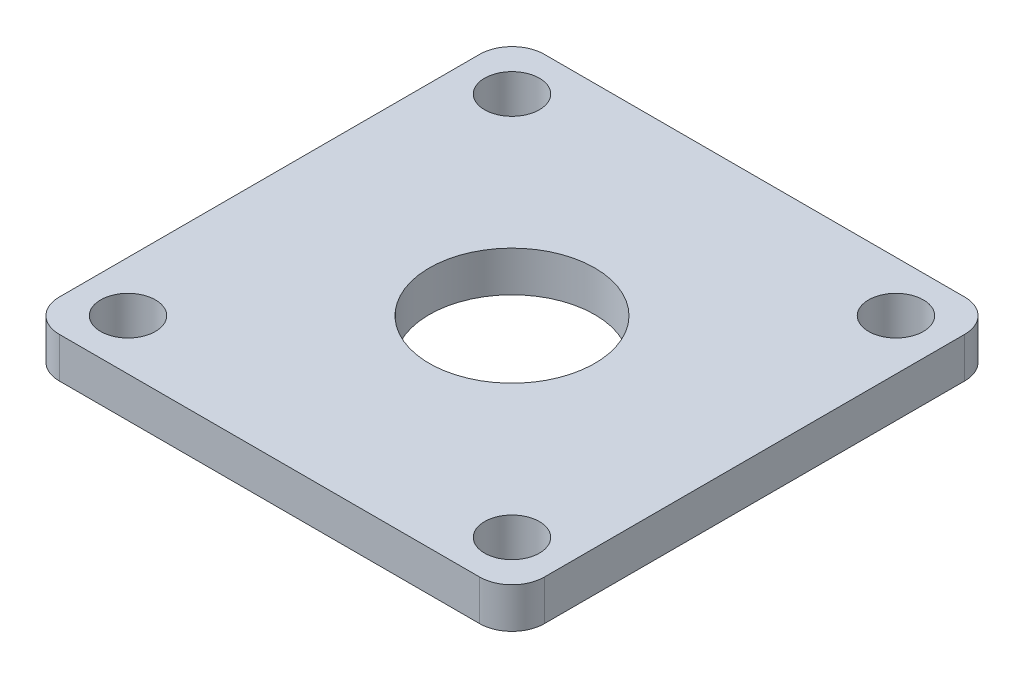
SolidWorks part; units mm, degrees
material "Alum Plate"
ref_plane "Front Plane" through (0, 0, 0) normal (0, 0, 1) x (1, 0, 0)
ref_plane "Top Plane" through (0, 0, 0) normal (0, 1, 0) x (1, 0, 0)
ref_plane "Right Plane" through (0, 0, 0) normal (1, 0, 0) x (0, 0, -1)
other "Bounding Box"
ref_plane "Default Plane" through (-8.9266, -12.7485, 0) normal (-0.1736, 0.9848, 0) x (0.9848, 0.1736, 0)
sketch "Sketch1" plane through (0, 0, 0) normal (0, 1, 0) x (1, 0, 0)
  line L0 (0, -12.5) -> (0, 12.5) construction
  line L1 (-14.5, 0) -> (0, 14.5) construction
  line L2 (-19.05, 19.05) -> (19.05, 19.05)
  line L3 (-19.05, 19.05) -> (-19.05, -19.05)
  line L4 (-19.05, -19.05) -> (19.05, -19.05)
  line L5 (19.05, 19.05) -> (19.05, -19.05)
  line L6 (-19.05, 19.05) -> (19.05, -19.05) construction
  line L7 (-19.05, -19.05) -> (19.05, 19.05) construction
  line L8 (8.8388, 8.8388) -> (-8.8388, 8.8388) construction
  line L9 (8.8388, 8.8388) -> (8.8388, -8.8388) construction
  line L10 (8.8388, -8.8388) -> (-8.8388, -8.8388) construction
  line L11 (-8.8388, 8.8388) -> (-8.8388, -8.8388) construction
  line L12 (8.8388, 8.8388) -> (-8.8388, -8.8388) construction
  line L13 (8.8388, -8.8388) -> (-8.8388, 8.8388) construction
  line L14 (-14.5, 0) -> (0, -14.5) construction
  line L15 (0, 14.5) -> (14.5, 0) construction
  line L16 (0, -14.5) -> (14.5, 0) construction
  line L17 (-14.5, 0) -> (14.5, 0) construction
  line L18 (0, 14.5) -> (0, -14.5) construction
  circle A0 centre (-15.24, 15.24) radius 1.3843 construction
  circle A1 centre (15.24, 15.24) radius 1.3843 construction
  circle A2 centre (15.24, -15.24) radius 1.3843 construction
  circle A3 centre (-15.24, -15.24) radius 1.3843 construction
  circle A4 centre (0, 0) radius 4
  circle A5 centre (8.8388, 8.8388) radius 1.5875
  circle A6 centre (8.8388, -8.8388) radius 1.5875
  circle A7 centre (-8.8388, -8.8388) radius 1.5875
  circle A8 centre (-8.8388, 8.8388) radius 1.5875
  circle A9 centre (-14.5, 0) radius 1.25
  circle A10 centre (0, 14.5) radius 1.25
  circle A11 centre (14.5, 0) radius 1.25
  circle A12 centre (0, -14.5) radius 1.25
  point P3 (0, 0)
  circle B0 centre (-9.8995, -9.8995) radius 1.2645 construction
  circle B1 centre (0, -8) radius 1.5875 construction
  circle B2 centre (0, 0) radius 4 construction
  circle B3 centre (9.8995, 9.8995) radius 1.2645 construction
  circle B4 centre (0, 8) radius 1.5875 construction
  circle B5 centre (9.8995, -9.8995) radius 1.2645 construction
  circle B6 centre (0, -12.5) radius 1.5875 construction
  circle B7 centre (-9.5, 0) radius 1.5875 construction
  circle B8 centre (-15.24, 15.24) radius 1.3843 construction
  circle B9 centre (15.24, 15.24) radius 1.3843 construction
  circle B10 centre (15.24, -15.24) radius 1.3843 construction
  circle B11 centre (-15.24, -15.24) radius 1.3843 construction
  circle B12 centre (9.5, 0) radius 1.5875 construction
  circle B13 centre (-9.8995, 9.8995) radius 1.2645 construction
  circle B14 centre (0, 12.5) radius 1.5875 construction
  dimension "D2" = 3.175
  dimension "D4" = 2.5
  dimension "D1" = 38.1
  dimension "D3" = 25
  dimension "D5" = 29
sketch_block_instance "Block-36mm gearbox motor block holes-1"
sketch_block "Block-36mm gearbox motor block holes"
extrude "Boss-Extrude1" add sketch "Sketch1" along normal mid plane 6.35 contours L5 L2 L3 L4 A12 A11 A9 A8 A10 A7 A6 A5 A4 A3 A2 A1 A0 region at (0, 0, -18.5112)
sketch "Sketch4" plane through (0, 0, 19.05) normal (0, 0, 1) x (1, 0, 0)
  line L0 (-5.5562, 0) -> (0, 0) construction
  line L1 (0, 0) -> (5.5562, 0) construction
  circle A0 centre (-5.5562, 0) radius 1.7272
  circle A1 centre (5.5562, 0) radius 1.7272
  dimension "D2" = 3.4544
  dimension "D1" = 11.1125
extrude "Cut-Extrude2" cut sketch "Sketch4" against normal blind 10.795
sketch "Sketch7" plane through (0, -3.175, 0) normal (0, -1, 0) x (1, 0, 0)
  line L0 (-19.05, 15.0813) -> (-15.0813, 15.0813) construction
  line L1 (-19.05, -19.05) -> (-19.05, 19.05) construction
  line L2 (-15.0813, 15.0813) -> (-15.0813, 19.05) construction
  line L3 (-19.05, 19.05) -> (19.05, 19.05) construction
  line L4 (0, 0) -> (-15.0813, 15.0813) construction
  line L5 (0, 0) -> (15.0813, 15.0812) construction
  circle A0 centre (-15.0813, 15.0813) radius 2.1526
  circle A1 centre (15.0813, 15.0812) radius 2.1527
  circle A2 centre (15.0812, -15.0813) radius 2.1527
  circle A3 centre (-15.0813, -15.0812) radius 2.1526
  dimension "D2" = 4.3053
  dimension "D1" = 3.9688
  dimension "D4" = 90
  dimension "D3" = 4
extrude "Cut-Extrude3" cut sketch "Sketch7" against normal through all
pattern_circular "CirPattern1" count 4 over 360 about axis through (0, 3.175, 0) along (0, -1, 0) of "Cut-Extrude2"
ref_plane "Plane1" through (0, -32.512, 0) normal (0, -1, 0) x (-1, 0, 0)
sketch "Sketch6" plane through (0, -32.512, 0) normal (0, -1, 0) x (-1, 0, 0)
  line L0 (19.05, 19.05) -> (-19.05, 19.05) construction
  line L1 (19.05, 19.05) -> (19.05, -19.05) construction
  line L2 (19.05, -19.05) -> (-19.05, -19.05) construction
  line L3 (-19.05, 19.05) -> (-19.05, -19.05) construction
  line L12 (19.05, 19.05) -> (-19.05, 19.05)
  line L13 (19.05, 19.05) -> (19.05, -19.05)
  line L14 (19.05, -19.05) -> (-19.05, -19.05)
  line L15 (-19.05, 19.05) -> (-19.05, -19.05)
  circle A8 centre (0, 0) radius 6.5
  circle A17 centre (-15.0812, 15.0813) radius 2.1526
  circle A18 centre (15.0813, 15.0812) radius 2.1526
  circle A19 centre (15.0813, -15.0813) radius 2.1527
  circle A20 centre (-15.0813, -15.0812) radius 2.1526
  circle A21 centre (-15.0812, 15.0813) radius 2.1527 construction
  dimension "D2" = 13
extrude "Boss-Extrude2" add sketch "Sketch6" along normal blind 3.175 separate body
fillet "Fillet1" radius 2.54 4 edges at (-19.05, 0, 19.05) (-19.05, 0, -19.05) (19.05, 0, -19.05) (19.05, 0, 19.05)
fillet "Fillet2" radius 2.54 4 edges at (-19.05, -34.0995, 19.05) (-19.05, -34.0995, -19.05) (19.05, -34.0995, -19.05) (19.05, -34.0995, 19.05)
sketch "Sketch8" [suppressed] plane through (0, -32.512, 0) normal (0, 1, 0) x (1, 0, 0)
  line L0 (-16.51, 19.05) -> (16.51, 19.05) construction
  circle A0 centre (-15.0813, 15.0812) radius 2.3876
  circle A1 centre (-15.0813, 15.0812) radius 3.9688
  dimension "D1" = 4.7752
extrude "Boss-Extrude3" [suppressed] add sketch "Sketch8" along normal offset from surface (4.572 mm away) 24.765 separate body up to face at (-15.0813, -3.175, -17.2339)
pattern_circular "CirPattern2" [suppressed] count 4 over 360 of bodies 110
delete or keep bodies "Body-Delete/Keep 1" type keep bodies bodies 108
delete or keep bodies "Body-Delete/Keep 2" [suppressed] type keep bodies bodies 107
delete or keep bodies "Body-Delete/Keep 3" [suppressed] bodies 113
delete or keep bodies "Body-Delete/Keep 4" [suppressed] type delete bodies bodies 107
sketch "Sketch9" [suppressed] plane through (0, 3.175, 0) normal (0, 1, 0) x (1, 0, 0)
  line L0 (-16.51, -19.05) -> (16.51, -19.05) construction
  line L1 (-19.05, 19.05) -> (19.05, 19.05)
  line L2 (-19.05, 19.05) -> (-19.05, -19.05)
  line L3 (-19.05, -19.05) -> (19.05, -19.05)
  line L4 (19.05, 19.05) -> (19.05, -19.05)
  line L5 (-19.05, 19.05) -> (19.05, -19.05) construction
  line L6 (-19.05, -19.05) -> (19.05, 19.05) construction
  point P0 (0, 0)
extrude "Boss-Extrude4" [suppressed] add sketch "Sketch9" along normal blind 9.525 from offset 27.559 separate body
sketch "Sketch12" [suppressed] plane through (0, 0, -19.05) normal (0, 0, -1) x (-1, 0, 0)
  line L0 (-19.05, 35.4965) -> (-9.525, 35.4965) construction
  line L1 (-19.05, 40.259) -> (-19.05, 30.734) construction
  line L2 (-9.525, 35.4965) -> (9.525, 35.4965) construction
  line L3 (9.525, 35.4965) -> (19.05, 35.4965) construction
  line L4 (19.05, 40.259) -> (19.05, 30.734) construction
  circle A0 centre (-9.525, 35.4965) radius 2.5
  circle A1 centre (9.525, 35.4965) radius 2.5
  dimension "D2" = 5
  dimension "D1" = 19.05
extrude "Cut-Extrude5" [suppressed] cut sketch "Sketch12" against normal blind 9.525
mirror "Mirror1" [suppressed] about plane through (0, 0, 0) normal (0, 0, 1)
fillet "Fillet3" [suppressed] radius 2.54
sketch "Sketch10" [suppressed] plane through (0, 40.259, 0) normal (0, 1, 0) x (1, 0, 0)
  line L1 (-9.8995, 9.8995) -> (9.8995, 9.8995) construction
  line L2 (-9.8995, 9.8995) -> (-9.8995, -9.8995) construction
  line L3 (-9.8995, -9.8995) -> (9.8995, -9.8995) construction
  line L4 (9.8995, 9.8995) -> (9.8995, -9.8995) construction
  line L5 (-9.8995, 9.8995) -> (9.8995, -9.8995) construction
  line L6 (-9.8995, -9.8995) -> (9.8995, 9.8995) construction
  line L7 (-15.0813, 15.0812) -> (15.0813, 15.0812) construction
  line L8 (-15.0813, 15.0812) -> (-15.0813, -15.0813) construction
  line L9 (-15.0813, -15.0813) -> (15.0813, -15.0813) construction
  line L10 (15.0813, 15.0812) -> (15.0813, -15.0813) construction
  line L11 (-15.0813, 15.0812) -> (15.0813, -15.0813) construction
  line L12 (-15.0813, -15.0813) -> (15.0813, 15.0812) construction
  circle A0 centre (0, 0) radius 11
  circle A1 centre (-9.8995, 9.8995) radius 1.5
  circle A2 centre (9.8995, 9.8995) radius 1.5
  circle A3 centre (9.8995, -9.8995) radius 1.5
  circle A4 centre (-9.8995, -9.8995) radius 1.5
  circle A5 centre (-15.0813, -15.0813) radius 2.2479
  circle A6 centre (-15.0813, 15.0812) radius 2.2479
  circle A7 centre (15.0813, 15.0812) radius 2.2479
  circle A8 centre (15.0813, -15.0813) radius 2.2479
  dimension "D2" = 22
  dimension "D4" = 4.4958
  dimension "D5" = 3
  dimension "D1" = 28
  dimension "D3" = 30.1625
extrude "Cut-Extrude4" [suppressed] cut sketch "Sketch10" against normal through all
delete or keep bodies "Body-Delete/Keep 5" [suppressed] type keep bodies bodies 115
